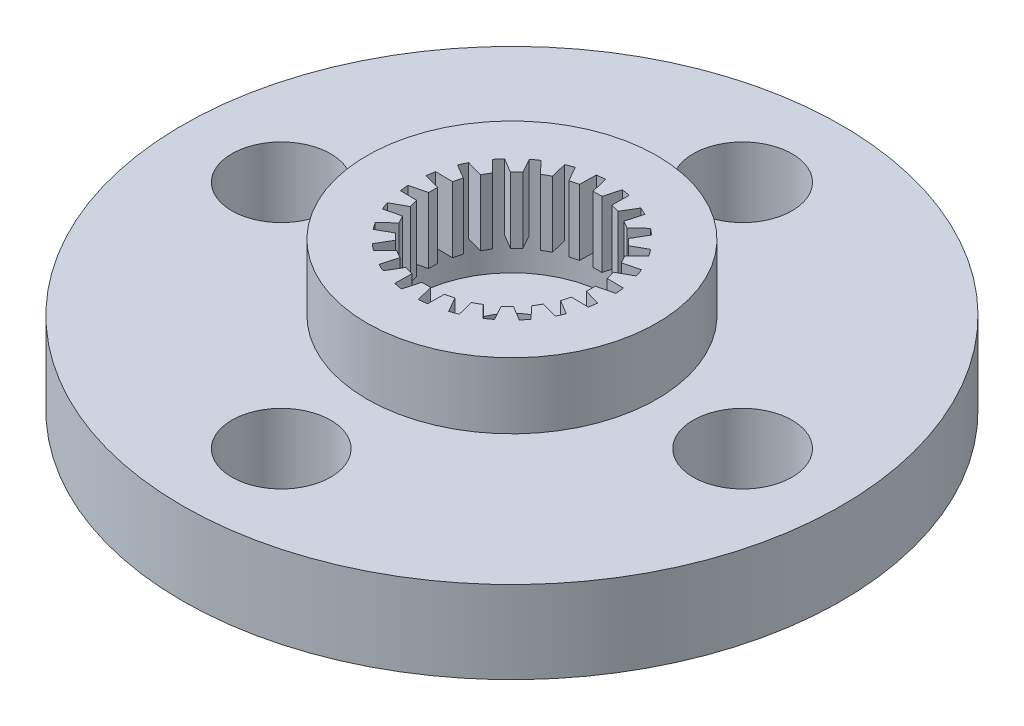
SolidWorks part; units mm, degrees
ref_plane "前视基准面" through (0, 0, 0) normal (0, 0, 1) x (1, 0, 0)
ref_plane "上视基准面" through (0, 0, 0) normal (0, 1, 0) x (1, 0, 0)
ref_plane "右视基准面" through (0, 0, 0) normal (1, 0, 0) x (0, 0, -1)
sketch "草图4" plane through (0, 0, 0) normal (0, 1, 0) x (1, 0, 0)
  circle A0 centre (0, 0) radius 10
  dimension "D1" = 20
extrude "凸台-拉伸2" add sketch "草图4" along normal blind 2.5
ref_plane "基准面7" through (0, 2.5, 0) normal (0, 1, 0) x (1, 0, 0)
sketch "草图6" plane through (0, 2.5, 0) normal (0, 1, 0) x (1, 0, 0)
  circle A0 centre (0, 0) radius 7 construction
  circle A1 centre (0, 7) radius 1.5
  circle A2 centre (0, 0) radius 1.5
  circle A3 centre (7, 0) radius 1.5
  circle A4 centre (-7, 0) radius 1.5
  circle A5 centre (0, -7) radius 1.5
  dimension "D1" = 3
  dimension "D2" = 3
  dimension "D3" = 3
  dimension "D4" = 3
  dimension "D5" = 3
  dimension "D6" = 14
extrude "切除-拉伸9" cut sketch "草图6" against normal blind 2.5
sketch "草图7" plane through (0, 2.5, 0) normal (0, 1, 0) x (1, 0, 0)
  circle A0 centre (0, 0) radius 4.4
  dimension "D1" = 8.8
extrude "凸台-拉伸3" add sketch "草图7" along normal blind 2
ref_plane "基准面8" through (0, 4.5, 0) normal (0, 1, 0) x (1, 0, 0)
sketch "草图8" plane through (0, 4.5, 0) normal (0, 1, 0) x (1, 0, 0)
  circle A0 centre (0, 0) radius 3
  dimension "D1" = 6
extrude "切除-拉伸10" cut sketch "草图8" against normal blind 3
ref_axis "基准轴1" through (0, 1.5, 0) along (0, 1, 0)
sketch "草图14" plane through (0, 4.5, 0) normal (0, 1, 0) x (1, 0, 0)
  line L0 (2.9769, -0.3715) -> (2.4958, -0.2354)
  line L1 (2.4958, -0.2354) -> (2.4958, 0.0323)
  line L2 (2.4958, 0.0323) -> (2.9958, 0.1588)
  arc A0 (2.9769, -0.3715) -> (2.9958, 0.1588) centre (0, 0) ccw
  dimension "D3" = 3
  dimension "D1" = 30
  dimension "D2" = 0.5
  dimension "0.5" = 0.5
extrude "凸台-拉伸5" add sketch "草图14" against normal blind 2
pattern_circular "阵列(圆周)1" count 24 over 360 about axis through (0, 4.5, 0) along (0, 1, 0) of "凸台-拉伸5"
sketch "草图15" plane through (0, 0, 0) normal (0, -1, 0) x (1, 0, 0)
  line L0 (7, 0) -> (0, 0) construction
  dimension "D1" = 7
